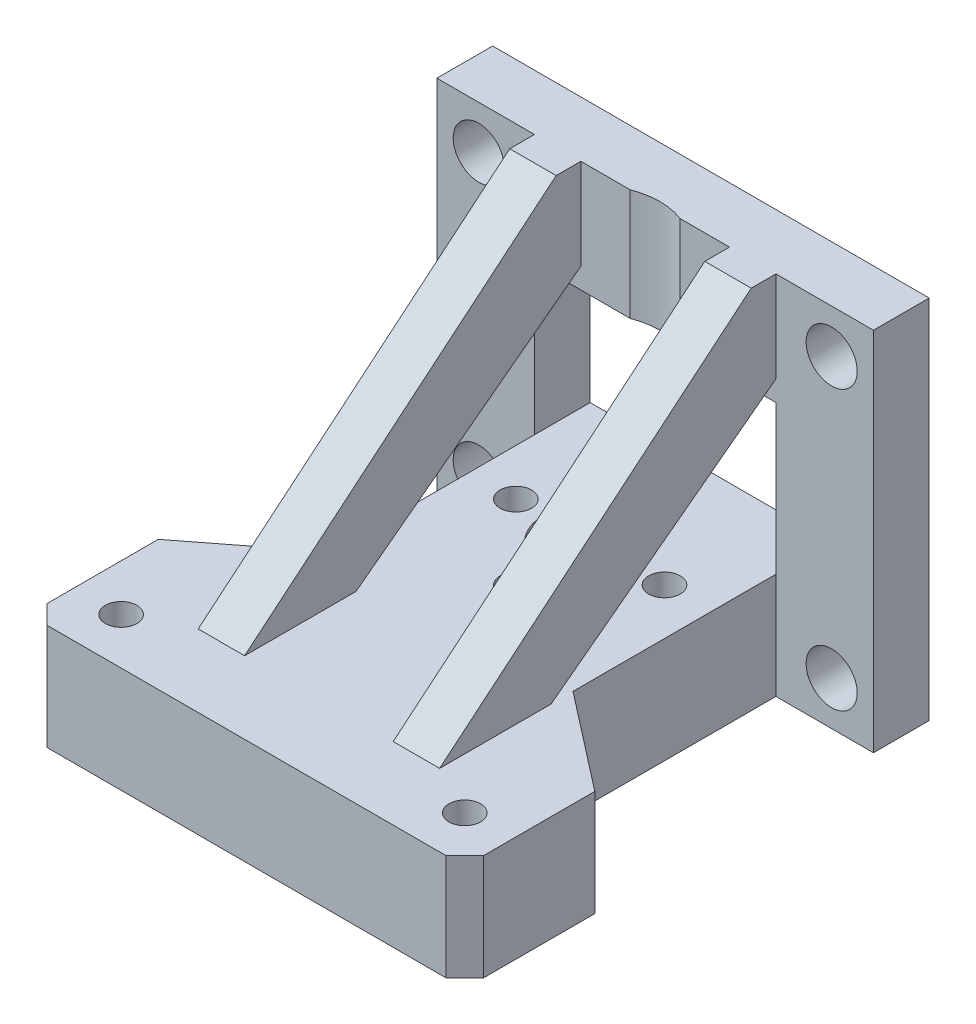
SolidWorks part; units mm, degrees
ref_plane "Front Plane" through (0, 0, 0) normal (0, 0, 1) x (1, 0, 0)
ref_plane "Top Plane" through (0, 0, 0) normal (0, 1, 0) x (1, 0, 0)
ref_plane "Right Plane" through (0, 0, 0) normal (1, 0, 0) x (0, 0, -1)
sketch "Sketch1" plane through (0, 0, 0) normal (0, 0, 1) x (1, 0, 0)
  line L1 (-23.5, -19.7) -> (23.5, -19.7)
  line L2 (-23.5, -19.7) -> (-23.5, 19.7)
  line L3 (-23.5, 19.7) -> (23.5, 19.7)
  line L4 (23.5, -19.7) -> (23.5, 19.7)
  line L5 (-23.5, -19.7) -> (23.5, 19.7) construction
  line L6 (-23.5, 19.7) -> (23.5, -19.7) construction
  point P0 (0, 0)
extrude "Boss-Extrude1" add sketch "Sketch1" along normal blind 50
sketch "Sketch2" plane through (0, 0, 0) normal (0, 0, -1) x (-1, 0, 0)
  line L0 (-23.5, 19.7) -> (23.5, 19.7) construction
  point P0 (19, 15)
  point P1 (-19, 15)
  point P2 (-19, -15)
  point P3 (19, -15)
sketch "Sketch3" plane through (0, 19.7, 0) normal (0, 1, 0) x (1, 0, 0)
  line L0 (0, 0) -> (0, -50) construction
  line L1 (23.5, -50) -> (23.5, 0) construction
  line L2 (23.5, -6) -> (13, -6)
  line L3 (13, -6) -> (13, -36)
  line L4 (13, -36) -> (23.5, -36)
  line L5 (23.5, -36) -> (23.5, -6)
  line L6 (23.5, 0) -> (-23.5, 0) construction
  line L7 (23.5, -50) -> (-23.5, -50) construction
  line L8 (-23.5, -36) -> (-23.5, -6)
  line L9 (-13, -36) -> (-23.5, -36)
  line L10 (-13, -6) -> (-13, -36)
  line L11 (-23.5, -6) -> (-13, -6)
extrude "Cut-Extrude1" cut sketch "Sketch3" against normal blind 50
sketch "Sketch19" plane through (0, -19.7, 0) normal (0, -1, 0) x (1, 0, 0)
  circle A0 centre (0, 13) radius 5
extrude "Cut-Extrude6" cut sketch "Sketch19" against normal through all
hole_wizard "M5 Clearance Hole1" positions "Sketch23" profile "Sketch24" hole size "M5" standard "ISO" end condition up to next
sketch "Sketch23" plane through (0, 0, 0) normal (0, 0, -1) x (-1, 0, 0)
  point P0 (-19, -15)
  point P3 (-19, 15)
  point P6 (19, 15)
  point P9 (19, -15)
sketch "Sketch24" plane through (19, -15, 0) normal (1, 0, 0) x (0, 1, 0)
  line L0 (0, 0) -> (0, 6)
  line L1 (0, 6) -> (2.75, 6)
  line L2 (2.75, 6) -> (2.75, 0)
  line L5 (2.75, 0) -> (0, 0)
  line L11 (0, -6.35) -> (0, 107.95) construction
  dimension "Thru Hole Dia." = 5.5
  dimension "Thru Hole Depth" = 6
sketch "Sketch25" plane through (0, 19.7, 0) normal (0, 1, 0) x (1, 0, 0)
  circle A0 centre (0, -13) radius 7.5
extrude "Cut-Extrude7" cut sketch "Sketch25" against normal blind 28 contours A0
sketch "Sketch26" plane through (0, 19.7, 0) normal (0, 1, 0) x (1, 0, 0)
  line L0 (13, -6) -> (13, -36)
  line L1 (13, -36) -> (23.5, -36)
  line L2 (23.5, -50) -> (23.5, -36) construction
  line L3 (13, -36) -> (23.5, -36) construction
  line L4 (23.5, -36) -> (23.5, -50)
  line L5 (23.5, -50) -> (-23.5, -50)
  line L6 (-23.5, -50) -> (-23.5, -36)
  line L7 (-23.5, -36) -> (-13, -36)
  line L8 (-13, -36) -> (-13, -6)
  line L9 (-13, -6) -> (13, -6)
extrude "Cut-Extrude8" cut sketch "Sketch26" against normal blind 28
sketch "Sketch27" plane through (0, 0, 6) normal (0, 0, 1) x (1, 0, 0)
  line L0 (13, -8.3) -> (-13, -8.3)
  line L1 (13, -8.3) -> (13, 7.7)
  line L2 (-13, -8.3) -> (-13, 7.7)
  line L3 (13, 7.7) -> (-13, 7.7)
extrude "Cut-Extrude9" cut sketch "Sketch27" against normal blind 28
sketch "Sketch28" plane through (0, -19.7, 0) normal (0, -1, 0) x (1, 0, 0)
  line L0 (0, 13) -> (0, 21) construction
  line L1 (0, 21) -> (0, 13) construction
  line L2 (0, 13) -> (8, 13) construction
  line L3 (0, 13) -> (0, 5) construction
  line L4 (0, 5) -> (0, 13) construction
  line L5 (0, 13) -> (-8, 13) construction
  line L6 (-23.5, 50) -> (-23.5, 36) construction
  line L7 (23.5, 50) -> (23.5, 36) construction
  line L10 (-23.5, 50) -> (23.5, 50) construction
  circle A0 centre (0, 21) radius 1.7
  circle A1 centre (8, 13) radius 1.7
  circle A2 centre (0, 5) radius 1.7
  circle A3 centre (-8, 13) radius 1.7
  circle A4 centre (-18.5, 45) radius 1.7
  circle A5 centre (18.5, 45) radius 1.7
  dimension "D1" = 5
  dimension "D2" = 5
  dimension "D3" = 5
  dimension "D4" = 5
extrude "Cut-Extrude10" cut sketch "Sketch28" against normal up to next
sketch "Sketch29" plane through (13, 0, 0) normal (1, 0, 0) x (0, 0, -1)
  line L0 (-42.2057, -8.3) -> (-30.2057, -8.3)
  line L1 (-36, -8.3) -> (-6, -8.3) construction
  line L2 (-30.2057, -8.3) -> (-6, 9.9198)
  line L3 (-6, 9.9198) -> (-6, 19.7)
  line L4 (-8.6595, 19.7) -> (-42.2057, -8.3)
  line L5 (-6, 19.7) -> (-8.6595, 19.7)
extrude "Boss-Extrude2" add sketch "Sketch29" against normal blind 26
sketch "Sketch30" plane through (0, 19.7, 0) normal (0, 1, 0) x (1, 0, 0)
  line L0 (13, -6) -> (8, -6) construction
  line L1 (-13, -6) -> (-8, -6) construction
  line L2 (8, -6) -> (-8, -6)
  line L3 (8, -6) -> (8, -47.7367)
  line L4 (-8, -6) -> (-8, -47.7367)
  line L5 (8, -47.7367) -> (-8, -47.7367)
extrude "Cut-Extrude11" cut sketch "Sketch30" against normal blind 28
sketch "Sketch31" plane through (0, -19.7, 0) normal (0, -1, 0) x (1, 0, 0)
  line L0 (-23.5, 36) -> (-13, 36)
  line L1 (-13, 36) -> (-13, 27.8469)
  line L2 (-13, 36) -> (-13, 6) construction
  line L3 (-13, 27.8469) -> (-23.5, 36)
  line L4 (13, 36) -> (13, 27.8469)
  line L5 (13, 6) -> (13, 36) construction
  line L6 (13, 27.8469) -> (23.5, 36)
  line L7 (23.5, 36) -> (13, 36)
extrude "Boss-Extrude3" add sketch "Sketch31" against normal up to vertex (11.4 mm away) up to point (23.5, -8.3, 36)
chamfer "Chamfer1" distance 2 angle 45 2 edges at (-23.5, -14, 50) (23.5, -14, 50)
